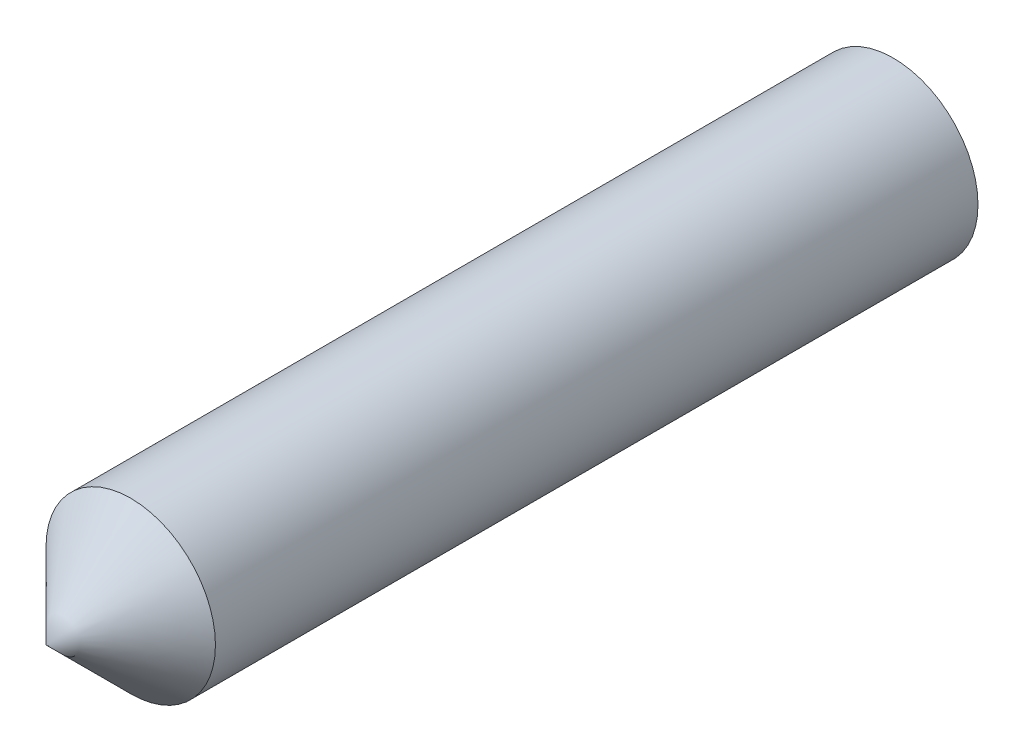
SolidWorks part; units mm, degrees
ref_plane "Front Plane" through (0, 0, 0) normal (0, 0, 1) x (1, 0, 0)
ref_plane "Top Plane" through (0, 0, 0) normal (0, 1, 0) x (1, 0, 0)
ref_plane "Right Plane" through (0, 0, 0) normal (1, 0, 0) x (0, 0, -1)
sketch "Sketch1" plane through (0, 0, 0) normal (0, 0, 1) x (1, 0, 0)
  circle A0 centre (0, 0) radius 5
  dimension "D1" = 10
extrude "Boss-Extrude1" add sketch "Sketch1" along normal blind 50
chamfer "Chamfer1" distance 5 angle 45 1 edges at (5, 0, 50)
